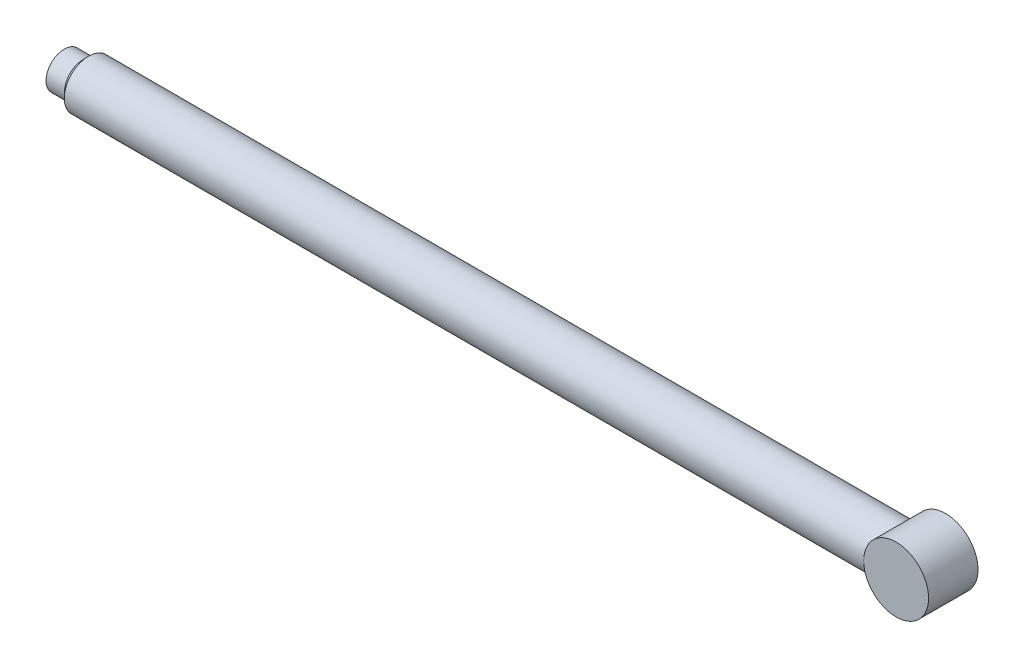
SolidWorks part; units mm, degrees
ref_plane "Front Plane" through (0, 0, 0) normal (0, 0, 1) x (1, 0, 0)
ref_plane "Top Plane" through (0, 0, 0) normal (0, 1, 0) x (1, 0, 0)
ref_plane "Right Plane" through (0, 0, 0) normal (1, 0, 0) x (0, 0, -1)
sketch "Sketch2" plane through (0, 0, 0) normal (1, 0, 0) x (0, 0, -1)
  circle A0 centre (0, 0) radius 150
  circle A1 centre (0, 0) radius 100
  dimension "D1" = 300
  dimension "D2" = 200
extrude "Boss-Extrude1" add sketch "Sketch2" along normal blind 5000
sketch "Sketch3" plane through (0, 0, 0) normal (-1, 0, 0) x (0, 0, 1)
  circle A0 centre (0, 0) radius 112.5
  circle A1 centre (0, 0) radius 92.5
  dimension "D1" = 225
  dimension "D2" = 185
extrude "Boss-Extrude2" add sketch "Sketch3" along normal blind 150
sketch "Sketch4" plane through (0, 0, 0) normal (0, 0, 1) x (1, 0, 0)
  circle A0 centre (5132.8297, 0) radius 200
  circle A1 centre (5132.8297, 0) radius 150
  point P2 (5131.7982, -3.8475)
  point P3 (5132.8297, 0)
  dimension "D1" = 400
  dimension "D2" = 300
extrude "Boss-Extrude9" add sketch "Sketch4" along normal through all and the other way through all separate body
sketch "Sketch5" plane through (0, 0, 150) normal (0, 0, 1) x (1, 0, 0)
  circle A0 centre (5132.8297, 0) radius 150
  dimension "D1" = 300
extrude "Cut-Extrude1" cut sketch "Sketch5" against normal blind 175
sketch "Sketch6" plane through (0, 0, 0) normal (-1, 0, 0) x (0, 0, 1)
  circle A0 centre (0, 0) radius 50
  dimension "D1" = 100
extrude "Cut-Extrude2" cut sketch "Sketch6" against normal blind 5024
sketch "Sketch7" plane through (0, 0, 0) normal (0, 0, 1) x (1, 0, 0)
  line L0 (0, 112.5) -> (0, 150)
  line L4 (-224.7945, 0) -> (133.1421, 0) construction
  line L5 (0, 112.5) -> (-35.5102, 112.5)
  line L6 (0, 112.5) -> (-150, 112.5) construction
  line L7 (-35.5102, 112.5) -> (0, 150)
  point P4 (-35.5102, 112.5)
revolve "Revolve1" add sketch "Sketch7" angle 360 about L4
sketch "Sketch9" plane through (0, 0, 150) normal (0, 0, 1) x (1, 0, 0)
  circle A0 centre (5132.8297, 0) radius 200
  point P3 (5050.1346, 0)
  point P4 (5050.1346, 0)
  dimension "D1" = 400
extrude "Boss-Extrude10" add sketch "Sketch9" along normal blind 5 and the other way blind 5
sketch "Sketch10" plane through (0, 0, -150) normal (0, 0, -1) x (-1, 0, 0)
  circle A0 centre (-5132.8297, 0) radius 150
  dimension "D1" = 300
extrude "Cut-Extrude3" cut sketch "Sketch10" against normal blind 202
